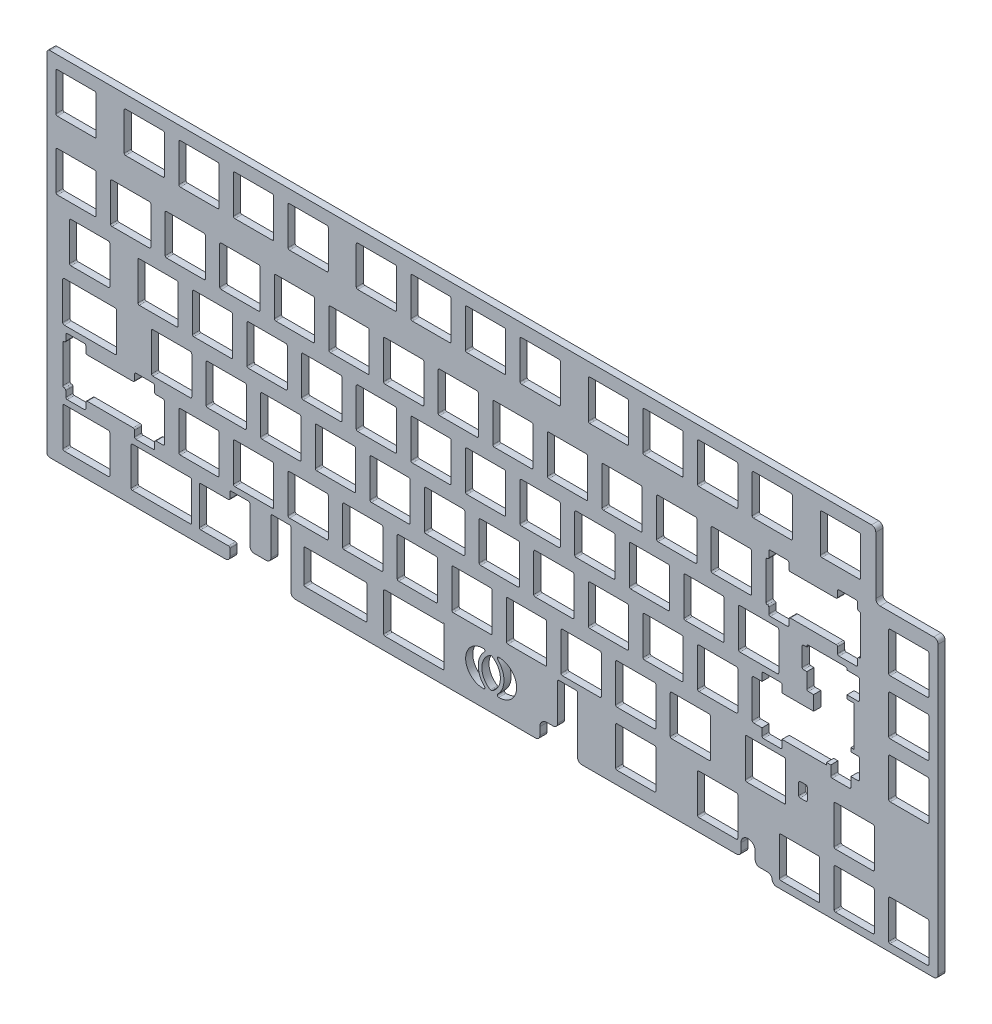
SolidWorks part; units mm, degrees
material "POM Acetal Copolymer"
ref_plane "Front Plane" through (0, 0, 0) normal (0, 0, 1) x (1, 0, 0)
ref_plane "Top Plane" through (0, 0, 0) normal (0, 1, 0) x (1, 0, 0)
ref_plane "Right Plane" through (0, 0, 0) normal (1, 0, 0) x (0, 0, -1)
sketch "Model" plane through (0, 0, 0) normal (0, 0, 1) x (1, 0, 0)
  line L0 (274.4928, 83.607) -> (287.4928, 83.607)
  line L1 (273.9928, 70.107) -> (273.9928, 75.3421)
  line L2 (8.8553, 129.8695) -> (8.8553, 63.082)
  line L3 (67.4518, 130.9695) -> (9.9553, 130.9695)
  line L4 (319.7678, 63.082) -> (319.7678, 106.4532)
  line L5 (195.4959, 7.957) -> (249.4928, 7.957)
  line L6 (86.9959, 28.958) -> (86.9959, 16.157)
  line L7 (187.4959, 29.458) -> (193.4959, 29.458)
  line L8 (193.9959, 28.958) -> (193.9959, 9.457)
  line L9 (186.9959, 16.157) -> (186.9959, 28.958)
  line L10 (87.4959, 29.458) -> (93.4959, 29.458)
  line L11 (126.357, 12.957) -> (126.357, 25.957)
  line L12 (62.0594, 12.957) -> (62.0594, 25.957)
  line L13 (38.2454, 12.957) -> (38.2454, 25.957)
  line L14 (14.4343, 12.957) -> (14.4343, 25.957)
  line L15 (72.207, 12.457) -> (62.5594, 12.457)
  line L16 (62.5594, 26.457) -> (72.207, 26.457)
  line L17 (59.3945, 25.957) -> (59.3945, 12.957)
  line L18 (58.8945, 12.457) -> (38.7454, 12.457)
  line L19 (38.7454, 26.457) -> (58.8945, 26.457)
  line L20 (30.8195, 25.957) -> (30.8195, 12.957)
  line L21 (30.3195, 12.457) -> (14.9343, 12.457)
  line L22 (14.9343, 26.457) -> (30.3195, 26.457)
  line L23 (93.9959, 28.958) -> (93.9959, 9.457)
  line L24 (146.9959, 12.457) -> (126.857, 12.457)
  line L25 (126.857, 26.457) -> (146.9959, 26.457)
  line L26 (147.4959, 26.7823) -> (147.4959, 12.957)
  line L27 (9.9553, 7.957) -> (71.207, 7.957)
  line L28 (95.4959, 7.957) -> (179.3625, 7.957)
  line L29 (263.3678, 5.0945) -> (318.2678, 5.0945)
  line L30 (180.8625, 12.157) -> (180.8625, 9.457)
  line L31 (250.9928, 12.157) -> (250.9928, 9.457)
  line L32 (255.9928, 12.157) -> (255.9928, 9.457)
  line L33 (183.3625, 14.657) -> (185.4959, 14.657)
  line L34 (81.207, 14.657) -> (85.4959, 14.657)
  line L35 (257.4928, 7.957) -> (260.371, 7.957)
  line L36 (8.8553, 63.082) -> (8.8553, 9.057)
  line L37 (319.7678, 63.082) -> (319.7678, 6.5945)
  line L38 (75.4518, 130.9695) -> (248.4268, 130.9695)
  line L39 (256.4268, 130.9695) -> (296.5553, 130.9695)
  line L40 (298.0553, 129.4695) -> (298.0553, 109.4532)
  line L41 (299.5553, 107.9532) -> (318.2678, 107.9532)
  line L42 (271.6572, 41.007) -> (273.6572, 41.007)
  line L43 (274.1572, 40.507) -> (274.1572, 36.507)
  line L44 (273.6572, 36.007) -> (271.6572, 36.007)
  line L45 (271.1572, 36.507) -> (271.1572, 40.507)
  line L46 (260.7295, 105.157) -> (260.7295, 103.157)
  line L47 (268.2295, 102.657) -> (284.2295, 102.657)
  line L48 (268.2295, 88.657) -> (284.2295, 88.657)
  line L49 (261.2295, 105.657) -> (267.2295, 105.657)
  line L50 (261.2295, 85.657) -> (267.2295, 85.657)
  line L51 (267.7295, 103.157) -> (267.7295, 105.157)
  line L52 (267.7295, 88.157) -> (267.7295, 86.157)
  line L53 (291.7295, 105.157) -> (291.7295, 103.157)
  line L54 (291.2295, 105.657) -> (285.2295, 105.657)
  line L55 (291.2295, 85.657) -> (285.2295, 85.657)
  line L56 (284.7295, 103.157) -> (284.7295, 105.157)
  line L57 (284.7295, 88.157) -> (284.7295, 86.157)
  line L58 (258.3508, 50.557) -> (258.3508, 48.057)
  line L59 (265.3508, 50.557) -> (280.8516, 50.557)
  line L60 (258.8508, 67.557) -> (264.8508, 67.557)
  line L61 (258.8508, 47.557) -> (264.8508, 47.557)
  line L62 (265.3508, 64.557) -> (265.3508, 67.057)
  line L63 (265.3508, 50.557) -> (265.3508, 48.057)
  line L64 (288.8508, 47.557) -> (282.8508, 47.557)
  line L65 (282.3508, 51.3421) -> (282.3508, 48.057)
  line L66 (15.4632, 48.0073) -> (15.4632, 46.007)
  line L67 (22.9632, 45.5073) -> (38.9632, 45.5073)
  line L68 (22.9632, 31.5073) -> (38.9632, 31.5073)
  line L69 (15.9632, 48.5073) -> (21.9632, 48.5073)
  line L70 (15.9632, 28.5073) -> (21.9632, 28.5073)
  line L71 (22.4632, 46.0073) -> (22.4632, 48.0073)
  line L72 (22.4632, 31.0073) -> (22.4632, 29.0073)
  line L73 (46.4632, 48.0073) -> (46.4632, 46.007)
  line L74 (45.9632, 48.5073) -> (39.9632, 48.5073)
  line L75 (45.9632, 28.5073) -> (39.9632, 28.5073)
  line L76 (39.4632, 46.0073) -> (39.4632, 48.0073)
  line L77 (39.4632, 31.0073) -> (39.4632, 29.0073)
  line L78 (258.3508, 50.557) -> (255.4453, 50.557)
  line L79 (276.3765, 69.607) -> (274.4928, 69.607)
  line L80 (276.3765, 64.557) -> (276.3765, 69.607)
  line L81 (292.3508, 82.2801) -> (292.3508, 75.8421)
  line L82 (292.3508, 58.2801) -> (292.3508, 51.8421)
  line L83 (291.8508, 82.7801) -> (287.9953, 82.7801)
  line L84 (255.4453, 64.557) -> (258.3508, 64.557)
  line L85 (290.3765, 74.0611) -> (290.3765, 60.0611)
  line L86 (254.9453, 64.057) -> (254.9453, 51.057)
  line L87 (287.9953, 75.3421) -> (291.8508, 75.3421)
  line L88 (289.3508, 58.7801) -> (291.8508, 58.7801)
  line L89 (290.3765, 74.0611) -> (287.9953, 74.0611)
  line L90 (287.9953, 74.0611) -> (287.9953, 75.3421)
  line L91 (289.3508, 58.7801) -> (289.3508, 60.0611)
  line L92 (289.3508, 60.0611) -> (290.3765, 60.0611)
  line L93 (282.3508, 51.3421) -> (280.8516, 51.3421)
  line L94 (280.8516, 51.3421) -> (280.8516, 50.557)
  line L95 (258.3508, 67.057) -> (258.3508, 64.557)
  line L96 (289.3508, 48.057) -> (289.3508, 51.3421)
  line L97 (291.8508, 51.3421) -> (289.3508, 51.3421)
  line L98 (287.9928, 83.107) -> (287.9953, 82.7801)
  line L99 (265.3508, 64.557) -> (276.3765, 64.557)
  line L100 (272.3508, 82.2801) -> (272.3508, 75.8421)
  line L101 (272.8508, 82.7801) -> (273.9928, 82.7801)
  line L102 (273.9928, 75.3421) -> (272.8508, 75.3421)
  line L103 (273.9928, 82.7801) -> (273.9928, 83.107)
  line L104 (259.7053, 89.157) -> (259.7053, 102.157)
  line L105 (292.7553, 102.157) -> (292.7553, 89.157)
  line L106 (291.7295, 86.157) -> (291.7295, 88.157)
  line L107 (292.2295, 88.657) -> (292.2553, 88.657)
  line L108 (292.2295, 102.657) -> (292.2553, 102.657)
  line L109 (260.2053, 102.657) -> (260.2295, 102.657)
  line L110 (260.7295, 86.157) -> (260.7295, 88.157)
  line L111 (260.2295, 88.657) -> (260.2053, 88.657)
  line L112 (49.8678, 45.007) -> (49.8678, 32.007)
  line L113 (46.4632, 29.0073) -> (46.4632, 31.007)
  line L114 (46.9632, 31.507) -> (49.3678, 31.507)
  line L115 (46.9632, 45.507) -> (49.3678, 45.507)
  line L116 (14.4365, 32.007) -> (14.4365, 45.007)
  line L117 (15.4632, 29.0073) -> (15.4632, 31.007)
  line L118 (14.9632, 31.507) -> (14.9365, 31.507)
  line L119 (14.9365, 45.507) -> (14.9632, 45.507)
  line L120 (79.707, 28.958) -> (79.707, 16.157)
  line L121 (72.707, 11.957) -> (72.707, 9.457)
  line L122 (72.707, 26.957) -> (72.707, 28.958)
  line L123 (73.207, 29.458) -> (79.207, 29.458)
  line L124 (120.5413, 13.957) -> (120.5413, 24.957)
  line L125 (99.0413, 13.457) -> (120.0413, 13.457)
  line L126 (98.5413, 24.957) -> (98.5413, 13.957)
  line L127 (120.0413, 25.457) -> (99.0413, 25.457)
  line L144 (12.5303, 112.4445) -> (25.5803, 112.4445)
  line L145 (26.0803, 112.9445) -> (26.0803, 125.9945)
  line L146 (25.5803, 126.4945) -> (12.5303, 126.4945)
  line L147 (12.0303, 125.9945) -> (12.0303, 112.9445)
  line L148 (36.3428, 112.4445) -> (49.3928, 112.4445)
  line L149 (49.8928, 112.9445) -> (49.8928, 125.9945)
  line L150 (49.3928, 126.4945) -> (36.3428, 126.4945)
  line L151 (35.8428, 125.9945) -> (35.8428, 112.9445)
  line L152 (93.4928, 112.4445) -> (106.5428, 112.4445)
  line L153 (107.0428, 112.9445) -> (107.0428, 125.9945)
  line L154 (106.5428, 126.4945) -> (93.4928, 126.4945)
  line L155 (92.9928, 125.9945) -> (92.9928, 112.9445)
  line L156 (117.3053, 112.4445) -> (130.3553, 112.4445)
  line L157 (130.8553, 112.9445) -> (130.8553, 125.9945)
  line L158 (130.3553, 126.4945) -> (117.3053, 126.4945)
  line L159 (116.8053, 125.9945) -> (116.8053, 112.9445)
  line L160 (136.3553, 112.4445) -> (149.4053, 112.4445)
  line L161 (149.9053, 112.9445) -> (149.9053, 125.9945)
  line L162 (149.4053, 126.4945) -> (136.3553, 126.4945)
  line L163 (135.8553, 125.9945) -> (135.8553, 112.9445)
  line L164 (155.4053, 112.4445) -> (168.4553, 112.4445)
  line L165 (168.9553, 112.9445) -> (168.9553, 125.9945)
  line L166 (168.4553, 126.4945) -> (155.4053, 126.4945)
  line L167 (154.9053, 125.9945) -> (154.9053, 112.9445)
  line L168 (174.4553, 112.4445) -> (187.5053, 112.4445)
  line L169 (188.0053, 112.9445) -> (188.0053, 125.9945)
  line L170 (187.5053, 126.4945) -> (174.4553, 126.4945)
  line L171 (173.9553, 125.9945) -> (173.9553, 112.9445)
  line L172 (198.2678, 112.4445) -> (211.3178, 112.4445)
  line L173 (211.8178, 112.9445) -> (211.8178, 125.9945)
  line L174 (211.3178, 126.4945) -> (198.2678, 126.4945)
  line L175 (197.7678, 125.9945) -> (197.7678, 112.9445)
  line L176 (217.3178, 112.4445) -> (230.3678, 112.4445)
  line L177 (230.8678, 112.9445) -> (230.8678, 125.9945)
  line L178 (230.3678, 126.4945) -> (217.3178, 126.4945)
  line L179 (216.8178, 125.9945) -> (216.8178, 112.9445)
  line L180 (279.2303, 112.4445) -> (292.2803, 112.4445)
  line L181 (292.7803, 112.9445) -> (292.7803, 125.9945)
  line L182 (292.2803, 126.4945) -> (279.2303, 126.4945)
  line L183 (278.7303, 125.9945) -> (278.7303, 112.9445)
  line L184 (303.0428, 88.632) -> (316.0928, 88.632)
  line L185 (316.5928, 89.132) -> (316.5928, 102.182)
  line L186 (316.0928, 102.682) -> (303.0428, 102.682)
  line L187 (302.5428, 102.182) -> (302.5428, 89.132)
  line L188 (283.9928, 26.7195) -> (297.0428, 26.7195)
  line L189 (297.5428, 27.2195) -> (297.5428, 40.2695)
  line L190 (297.0428, 40.7695) -> (283.9928, 40.7695)
  line L191 (283.4928, 40.2695) -> (283.4928, 27.2195)
  line L192 (303.0428, 7.6695) -> (316.0928, 7.6695)
  line L193 (316.5928, 8.1695) -> (316.5928, 21.2195)
  line L194 (316.0928, 21.7195) -> (303.0428, 21.7195)
  line L195 (302.5428, 21.2195) -> (302.5428, 8.1695)
  line L196 (283.9928, 7.6695) -> (297.0428, 7.6695)
  line L197 (297.5428, 8.1695) -> (297.5428, 21.2195)
  line L198 (297.0428, 21.7195) -> (283.9928, 21.7195)
  line L199 (283.4928, 21.2195) -> (283.4928, 8.1695)
  line L200 (264.9428, 7.6695) -> (277.9928, 7.6695)
  line L201 (278.4928, 8.1695) -> (278.4928, 21.2195)
  line L202 (277.9928, 21.7195) -> (264.9428, 21.7195)
  line L203 (264.4428, 21.2195) -> (264.4428, 8.1695)
  line L204 (236.3678, 12.432) -> (249.4178, 12.432)
  line L205 (249.9178, 12.932) -> (249.9178, 25.982)
  line L206 (249.4178, 26.482) -> (236.3678, 26.482)
  line L207 (235.8678, 25.982) -> (235.8678, 12.932)
  line L208 (207.7928, 12.432) -> (220.8428, 12.432)
  line L209 (221.3428, 12.932) -> (221.3428, 25.982)
  line L210 (220.8428, 26.482) -> (207.7928, 26.482)
  line L211 (207.2928, 25.982) -> (207.2928, 12.932)
  line L212 (253.0365, 31.482) -> (266.0865, 31.482)
  line L213 (266.5865, 31.982) -> (266.5865, 45.032)
  line L214 (266.0865, 45.532) -> (253.0365, 45.532)
  line L215 (252.5365, 45.032) -> (252.5365, 31.982)
  line L216 (226.8428, 31.482) -> (239.8928, 31.482)
  line L217 (240.3928, 31.982) -> (240.3928, 45.032)
  line L218 (239.8928, 45.532) -> (226.8428, 45.532)
  line L219 (226.3428, 45.032) -> (226.3428, 31.982)
  line L220 (207.7928, 31.482) -> (220.8428, 31.482)
  line L221 (221.3428, 31.982) -> (221.3428, 45.032)
  line L222 (220.8428, 45.532) -> (207.7928, 45.532)
  line L223 (207.2928, 45.032) -> (207.2928, 31.982)
  line L224 (188.7428, 31.482) -> (201.7928, 31.482)
  line L225 (202.2928, 31.982) -> (202.2928, 45.032)
  line L226 (201.7928, 45.532) -> (188.7428, 45.532)
  line L227 (188.2428, 45.032) -> (188.2428, 31.982)
  line L228 (169.6928, 31.482) -> (182.7428, 31.482)
  line L229 (183.2428, 31.982) -> (183.2428, 45.032)
  line L230 (182.7428, 45.532) -> (169.6928, 45.532)
  line L231 (169.1928, 45.032) -> (169.1928, 31.982)
  line L232 (150.6428, 31.482) -> (163.6928, 31.482)
  line L233 (164.1928, 31.982) -> (164.1928, 45.032)
  line L234 (163.6928, 45.532) -> (150.6428, 45.532)
  line L235 (150.1428, 45.032) -> (150.1428, 31.982)
  line L236 (131.5928, 31.482) -> (144.6428, 31.482)
  line L237 (145.1428, 31.982) -> (145.1428, 45.032)
  line L238 (144.6428, 45.532) -> (131.5928, 45.532)
  line L239 (131.0928, 45.032) -> (131.0928, 31.982)
  line L240 (112.5428, 31.482) -> (125.5928, 31.482)
  line L241 (126.0928, 31.982) -> (126.0928, 45.032)
  line L242 (125.5928, 45.532) -> (112.5428, 45.532)
  line L243 (112.0428, 45.032) -> (112.0428, 31.982)
  line L244 (93.4928, 31.482) -> (106.5428, 31.482)
  line L245 (107.0428, 31.982) -> (107.0428, 45.032)
  line L246 (106.5428, 45.532) -> (93.4928, 45.532)
  line L247 (92.9928, 45.032) -> (92.9928, 31.982)
  line L248 (74.4428, 31.482) -> (87.4928, 31.482)
  line L249 (87.9928, 31.982) -> (87.9928, 45.032)
  line L250 (87.4928, 45.532) -> (74.4428, 45.532)
  line L251 (73.9428, 45.032) -> (73.9428, 31.982)
  line L252 (55.3928, 31.482) -> (68.4428, 31.482)
  line L253 (68.9428, 31.982) -> (68.9428, 45.032)
  line L254 (68.4428, 45.532) -> (55.3928, 45.532)
  line L255 (54.8928, 45.032) -> (54.8928, 31.982)
  line L256 (45.8678, 50.532) -> (58.9178, 50.532)
  line L257 (59.4178, 51.032) -> (59.4178, 64.082)
  line L258 (58.9178, 64.582) -> (45.8678, 64.582)
  line L259 (45.3678, 64.082) -> (45.3678, 51.032)
  line L260 (64.9178, 50.532) -> (77.9678, 50.532)
  line L261 (78.4678, 51.032) -> (78.4678, 64.082)
  line L262 (77.9678, 64.582) -> (64.9178, 64.582)
  line L263 (64.4178, 64.082) -> (64.4178, 51.032)
  line L264 (83.9678, 50.532) -> (97.0178, 50.532)
  line L265 (97.5178, 51.032) -> (97.5178, 64.082)
  line L266 (97.0178, 64.582) -> (83.9678, 64.582)
  line L267 (83.4678, 64.082) -> (83.4678, 51.032)
  line L268 (103.0178, 50.532) -> (116.0678, 50.532)
  line L269 (116.5678, 51.032) -> (116.5678, 64.082)
  line L270 (116.0678, 64.582) -> (103.0178, 64.582)
  line L271 (102.5178, 64.082) -> (102.5178, 51.032)
  line L272 (122.0678, 50.532) -> (135.1178, 50.532)
  line L273 (135.6178, 51.032) -> (135.6178, 64.082)
  line L274 (135.1178, 64.582) -> (122.0678, 64.582)
  line L275 (121.5678, 64.082) -> (121.5678, 51.032)
  line L276 (141.1178, 50.532) -> (154.1678, 50.532)
  line L277 (154.6678, 51.032) -> (154.6678, 64.082)
  line L278 (154.1678, 64.582) -> (141.1178, 64.582)
  line L279 (140.6178, 64.082) -> (140.6178, 51.032)
  line L280 (160.1678, 50.532) -> (173.2178, 50.532)
  line L281 (173.7178, 51.032) -> (173.7178, 64.082)
  line L282 (173.2178, 64.582) -> (160.1678, 64.582)
  line L283 (159.6678, 64.082) -> (159.6678, 51.032)
  line L284 (179.2178, 50.532) -> (192.2678, 50.532)
  line L285 (192.7678, 51.032) -> (192.7678, 64.082)
  line L286 (192.2678, 64.582) -> (179.2178, 64.582)
  line L287 (178.7178, 64.082) -> (178.7178, 51.032)
  line L288 (198.2678, 50.532) -> (211.3178, 50.532)
  line L289 (211.8178, 51.032) -> (211.8178, 64.082)
  line L290 (211.3178, 64.582) -> (198.2678, 64.582)
  line L291 (197.7678, 64.082) -> (197.7678, 51.032)
  line L292 (217.3178, 50.532) -> (230.3678, 50.532)
  line L293 (230.8678, 51.032) -> (230.8678, 64.082)
  line L294 (230.3678, 64.582) -> (217.3178, 64.582)
  line L295 (216.8178, 64.082) -> (216.8178, 51.032)
  line L296 (236.3678, 50.532) -> (249.4178, 50.532)
  line L297 (249.9178, 51.032) -> (249.9178, 64.082)
  line L298 (249.4178, 64.582) -> (236.3678, 64.582)
  line L299 (235.8678, 64.082) -> (235.8678, 51.032)
  line L300 (17.2928, 69.582) -> (30.3428, 69.582)
  line L301 (30.8428, 70.082) -> (30.8428, 83.132)
  line L302 (30.3428, 83.632) -> (17.2928, 83.632)
  line L303 (16.7928, 83.132) -> (16.7928, 70.082)
  line L304 (12.5303, 88.632) -> (25.5803, 88.632)
  line L305 (26.0803, 89.132) -> (26.0803, 102.182)
  line L306 (25.5803, 102.682) -> (12.5303, 102.682)
  line L307 (12.0303, 102.182) -> (12.0303, 89.132)
  line L308 (31.5803, 88.632) -> (44.6303, 88.632)
  line L309 (45.1303, 89.132) -> (45.1303, 102.182)
  line L310 (44.6303, 102.682) -> (31.5803, 102.682)
  line L311 (31.0803, 102.182) -> (31.0803, 89.132)
  line L312 (50.6303, 88.632) -> (63.6803, 88.632)
  line L313 (64.1803, 89.132) -> (64.1803, 102.182)
  line L314 (63.6803, 102.682) -> (50.6303, 102.682)
  line L315 (50.1303, 102.182) -> (50.1303, 89.132)
  line L316 (69.6803, 88.632) -> (82.7303, 88.632)
  line L317 (83.2303, 89.132) -> (83.2303, 102.182)
  line L318 (82.7303, 102.682) -> (69.6803, 102.682)
  line L319 (69.1803, 102.182) -> (69.1803, 89.132)
  line L320 (88.7303, 88.632) -> (101.7803, 88.632)
  line L321 (102.2803, 89.132) -> (102.2803, 102.182)
  line L322 (101.7803, 102.682) -> (88.7303, 102.682)
  line L323 (88.2303, 102.182) -> (88.2303, 89.132)
  line L324 (107.7803, 88.632) -> (120.8303, 88.632)
  line L325 (121.3303, 89.132) -> (121.3303, 102.182)
  line L326 (120.8303, 102.682) -> (107.7803, 102.682)
  line L327 (107.2803, 102.182) -> (107.2803, 89.132)
  line L328 (126.8303, 88.632) -> (139.8803, 88.632)
  line L329 (140.3803, 89.132) -> (140.3803, 102.182)
  line L330 (139.8803, 102.682) -> (126.8303, 102.682)
  line L331 (126.3303, 102.182) -> (126.3303, 89.132)
  line L332 (145.8803, 88.632) -> (158.9303, 88.632)
  line L333 (159.4303, 89.132) -> (159.4303, 102.182)
  line L334 (158.9303, 102.682) -> (145.8803, 102.682)
  line L335 (145.3803, 102.182) -> (145.3803, 89.132)
  line L336 (164.9303, 88.632) -> (177.9803, 88.632)
  line L337 (178.4803, 89.132) -> (178.4803, 102.182)
  line L338 (177.9803, 102.682) -> (164.9303, 102.682)
  line L339 (164.4303, 102.182) -> (164.4303, 89.132)
  line L340 (183.9803, 88.632) -> (197.0303, 88.632)
  line L341 (197.5303, 89.132) -> (197.5303, 102.182)
  line L342 (197.0303, 102.682) -> (183.9803, 102.682)
  line L343 (183.4803, 102.182) -> (183.4803, 89.132)
  line L344 (203.0303, 88.632) -> (216.0803, 88.632)
  line L345 (216.5803, 89.132) -> (216.5803, 102.182)
  line L346 (216.0803, 102.682) -> (203.0303, 102.682)
  line L347 (202.5303, 102.182) -> (202.5303, 89.132)
  line L348 (222.0803, 88.632) -> (235.1303, 88.632)
  line L349 (235.6303, 89.132) -> (235.6303, 102.182)
  line L350 (235.1303, 102.682) -> (222.0803, 102.682)
  line L351 (221.5803, 102.182) -> (221.5803, 89.132)
  line L352 (241.1303, 88.632) -> (254.1803, 88.632)
  line L353 (254.6803, 89.132) -> (254.6803, 102.182)
  line L354 (254.1803, 102.682) -> (241.1303, 102.682)
  line L355 (240.6303, 102.182) -> (240.6303, 89.132)
  line L356 (41.1053, 69.582) -> (54.1553, 69.582)
  line L357 (54.6553, 70.082) -> (54.6553, 83.132)
  line L358 (54.1553, 83.632) -> (41.1053, 83.632)
  line L359 (40.6053, 83.132) -> (40.6053, 70.082)
  line L360 (60.1553, 69.582) -> (73.2053, 69.582)
  line L361 (73.7053, 70.082) -> (73.7053, 83.132)
  line L362 (73.2053, 83.632) -> (60.1553, 83.632)
  line L363 (59.6553, 83.132) -> (59.6553, 70.082)
  line L364 (79.2053, 69.582) -> (92.2553, 69.582)
  line L365 (92.7553, 70.082) -> (92.7553, 83.132)
  line L366 (92.2553, 83.632) -> (79.2053, 83.632)
  line L367 (78.7053, 83.132) -> (78.7053, 70.082)
  line L368 (98.2553, 69.582) -> (111.3053, 69.582)
  line L369 (111.8053, 70.082) -> (111.8053, 83.132)
  line L370 (111.3053, 83.632) -> (98.2553, 83.632)
  line L371 (97.7553, 83.132) -> (97.7553, 70.082)
  line L372 (117.3053, 69.582) -> (130.3553, 69.582)
  line L373 (130.8553, 70.082) -> (130.8553, 83.132)
  line L374 (130.3553, 83.632) -> (117.3053, 83.632)
  line L375 (116.8053, 83.132) -> (116.8053, 70.082)
  line L376 (136.3553, 69.582) -> (149.4053, 69.582)
  line L377 (149.9053, 70.082) -> (149.9053, 83.132)
  line L378 (149.4053, 83.632) -> (136.3553, 83.632)
  line L379 (135.8553, 83.132) -> (135.8553, 70.082)
  line L380 (155.4053, 69.582) -> (168.4553, 69.582)
  line L381 (168.9553, 70.082) -> (168.9553, 83.132)
  line L382 (168.4553, 83.632) -> (155.4053, 83.632)
  line L383 (154.9053, 83.132) -> (154.9053, 70.082)
  line L384 (174.4553, 69.582) -> (187.5053, 69.582)
  line L385 (188.0053, 70.082) -> (188.0053, 83.132)
  line L386 (187.5053, 83.632) -> (174.4553, 83.632)
  line L387 (173.9553, 83.132) -> (173.9553, 70.082)
  line L388 (193.5053, 69.582) -> (206.5553, 69.582)
  line L389 (207.0553, 70.082) -> (207.0553, 83.132)
  line L390 (206.5553, 83.632) -> (193.5053, 83.632)
  line L391 (193.0053, 83.132) -> (193.0053, 70.082)
  line L392 (212.5553, 69.582) -> (225.6053, 69.582)
  line L393 (226.1053, 70.082) -> (226.1053, 83.132)
  line L394 (225.6053, 83.632) -> (212.5553, 83.632)
  line L395 (212.0553, 83.132) -> (212.0553, 70.082)
  line L396 (231.6053, 69.582) -> (244.6553, 69.582)
  line L397 (245.1553, 70.082) -> (245.1553, 83.132)
  line L398 (244.6553, 83.632) -> (231.6053, 83.632)
  line L399 (231.1053, 83.132) -> (231.1053, 70.082)
  line L400 (250.6553, 69.582) -> (263.7053, 69.582)
  line L401 (264.2053, 70.082) -> (264.2053, 83.132)
  line L402 (263.7053, 83.632) -> (250.6553, 83.632)
  line L403 (250.1553, 83.132) -> (250.1553, 70.082)
  line L404 (303.0428, 69.582) -> (316.0928, 69.582)
  line L405 (316.5928, 70.082) -> (316.5928, 83.132)
  line L406 (316.0928, 83.632) -> (303.0428, 83.632)
  line L407 (302.5428, 83.132) -> (302.5428, 70.082)
  line L408 (303.0678, 64.582) -> (316.1178, 64.582)
  line L409 (302.5428, 51.057) -> (302.5428, 64.057)
  line L410 (316.0678, 50.532) -> (303.0678, 50.532)
  line L411 (316.5928, 64.107) -> (316.5928, 51.057)
  line L412 (32.699, 50.507) -> (14.9365, 50.507)
  line L413 (33.249, 64.057) -> (33.249, 51.057)
  line L414 (14.9365, 64.607) -> (32.699, 64.607)
  line L415 (14.3865, 51.057) -> (14.3865, 64.057)
  line L416 (236.3678, 112.4445) -> (249.4178, 112.4445)
  line L417 (249.9178, 112.9445) -> (249.9178, 125.9945)
  line L418 (249.4178, 126.4945) -> (236.3678, 126.4945)
  line L419 (235.8678, 125.9945) -> (235.8678, 112.9445)
  line L420 (255.4178, 112.4445) -> (268.4678, 112.4445)
  line L421 (268.9678, 112.9445) -> (268.9678, 125.9945)
  line L422 (268.4678, 126.4945) -> (255.4178, 126.4945)
  line L423 (254.9178, 125.9945) -> (254.9178, 112.9445)
  line L424 (55.3928, 112.4445) -> (68.4428, 112.4445)
  line L425 (68.9428, 112.9445) -> (68.9428, 125.9945)
  line L426 (68.4428, 126.4945) -> (55.3928, 126.4945)
  line L427 (54.8928, 125.9945) -> (54.8928, 112.9445)
  line L428 (74.4428, 112.4445) -> (87.4928, 112.4445)
  line L429 (87.9928, 112.9445) -> (87.9928, 125.9945)
  line L430 (87.4928, 126.4945) -> (74.4428, 126.4945)
  line L431 (73.9428, 125.9945) -> (73.9428, 112.9445)
  line L432 (67.4518, 130.9695) -> (75.4518, 130.9695)
  line L433 (248.4268, 130.9695) -> (256.4268, 130.9695)
  arc A0 (319.7678, 106.4532) -> (318.2678, 107.9532) centre (318.2678, 106.4532) ccw
  arc A1 (318.2678, 5.0945) -> (319.7678, 6.5945) centre (318.2678, 6.5945) ccw
  arc A2 (193.9959, 9.457) -> (195.4959, 7.957) centre (195.4959, 9.457) ccw
  arc A3 (273.9928, 70.107) -> (274.4928, 69.607) centre (274.4928, 70.107) ccw
  arc A4 (287.9928, 83.107) -> (287.4928, 83.607) centre (287.4928, 83.107) ccw
  arc A5 (274.4928, 83.607) -> (273.9928, 83.107) centre (274.4928, 83.107) ccw
  arc A6 (8.8553, 9.057) -> (9.9553, 7.957) centre (9.9553, 9.057) ccw
  arc A7 (9.9553, 130.9695) -> (8.8553, 129.8695) centre (9.9553, 129.8695) ccw
  arc A8 (85.4959, 14.657) -> (86.9959, 16.157) centre (85.4959, 16.157) ccw
  arc A9 (193.9959, 28.958) -> (193.4959, 29.458) centre (193.4959, 28.958) ccw
  arc A10 (187.4959, 29.458) -> (186.9959, 28.958) centre (187.4959, 28.958) ccw
  arc A11 (185.4959, 14.657) -> (186.9959, 16.157) centre (185.4959, 16.157) ccw
  arc A12 (87.4959, 29.458) -> (86.9959, 28.958) centre (87.4959, 28.958) ccw
  arc A13 (126.357, 12.957) -> (126.857, 12.457) centre (126.857, 12.957) ccw
  arc A14 (93.9959, 28.958) -> (93.4959, 29.458) centre (93.4959, 28.958) ccw
  arc A15 (38.7454, 26.457) -> (38.2454, 25.957) centre (38.7454, 25.957) ccw
  arc A16 (14.9343, 26.457) -> (14.4343, 25.957) centre (14.9343, 25.957) ccw
  arc A17 (62.0594, 12.957) -> (62.5594, 12.457) centre (62.5594, 12.957) ccw
  arc A18 (62.5594, 26.457) -> (62.0594, 25.957) centre (62.5594, 25.957) ccw
  arc A19 (38.2454, 12.957) -> (38.7454, 12.457) centre (38.7454, 12.957) ccw
  arc A20 (58.8945, 12.457) -> (59.3945, 12.957) centre (58.8945, 12.957) ccw
  arc A21 (59.3945, 25.957) -> (58.8945, 26.457) centre (58.8945, 25.957) ccw
  arc A22 (30.3195, 12.457) -> (30.8195, 12.957) centre (30.3195, 12.957) ccw
  arc A23 (14.4343, 12.957) -> (14.9343, 12.457) centre (14.9343, 12.957) ccw
  arc A24 (30.8195, 25.957) -> (30.3195, 26.457) centre (30.3195, 25.957) ccw
  arc A25 (126.857, 26.457) -> (126.357, 25.957) centre (126.857, 25.957) ccw
  arc A26 (146.9959, 12.457) -> (147.4959, 12.957) centre (146.9959, 12.957) ccw
  arc A27 (147.4959, 26.7823) -> (146.9959, 26.457) centre (147.4647, 26.2833) ccw
  arc A28 (93.9959, 9.457) -> (95.4959, 7.957) centre (95.4959, 9.457) ccw
  arc A29 (261.8694, 6.5258) -> (263.3678, 5.0945) centre (263.3678, 6.5945) ccw
  arc A30 (261.8694, 6.5258) -> (260.371, 7.957) centre (260.371, 6.457) ccw
  arc A31 (179.3625, 7.957) -> (180.8625, 9.457) centre (179.3625, 9.457) ccw
  arc A32 (255.9928, 9.457) -> (257.4928, 7.957) centre (257.4928, 9.457) ccw
  arc A33 (249.4928, 7.957) -> (250.9928, 9.457) centre (249.4928, 9.457) ccw
  arc A34 (255.9928, 12.157) -> (250.9928, 12.157) centre (253.4928, 12.157) ccw
  arc A35 (183.3625, 14.657) -> (180.8625, 12.157) centre (183.3625, 12.157) ccw
  arc A36 (298.0553, 129.4695) -> (296.5553, 130.9695) centre (296.5553, 129.4695) ccw
  arc A37 (298.0553, 109.4532) -> (299.5553, 107.9532) centre (299.5553, 109.4532) ccw
  arc A38 (271.6572, 41.007) -> (271.1572, 40.507) centre (271.6572, 40.507) ccw
  arc A39 (274.1572, 40.507) -> (273.6572, 41.007) centre (273.6572, 40.507) ccw
  arc A40 (273.6572, 36.007) -> (274.1572, 36.507) centre (273.6572, 36.507) ccw
  arc A41 (271.1572, 36.507) -> (271.6572, 36.007) centre (271.6572, 36.507) ccw
  arc A42 (260.2295, 102.657) -> (260.7295, 103.157) centre (260.2295, 103.157) ccw
  arc A43 (267.7295, 103.157) -> (268.2295, 102.657) centre (268.2295, 103.157) ccw
  arc A44 (261.2295, 105.657) -> (260.7295, 105.157) centre (261.2295, 105.157) ccw
  arc A45 (260.7295, 86.157) -> (261.2295, 85.657) centre (261.2295, 86.157) ccw
  arc A46 (267.7295, 105.157) -> (267.2295, 105.657) centre (267.2295, 105.157) ccw
  arc A47 (268.2295, 88.657) -> (267.7295, 88.157) centre (268.2295, 88.157) ccw
  arc A48 (267.2295, 85.657) -> (267.7295, 86.157) centre (267.2295, 86.157) ccw
  arc A49 (284.2295, 102.657) -> (284.7295, 103.157) centre (284.2295, 103.157) ccw
  arc A50 (291.7295, 105.157) -> (291.2295, 105.657) centre (291.2295, 105.157) ccw
  arc A51 (291.2295, 85.657) -> (291.7295, 86.157) centre (291.2295, 86.157) ccw
  arc A52 (285.2295, 105.657) -> (284.7295, 105.157) centre (285.2295, 105.157) ccw
  arc A53 (284.7295, 88.157) -> (284.2295, 88.657) centre (284.2295, 88.157) ccw
  arc A54 (284.7295, 86.157) -> (285.2295, 85.657) centre (285.2295, 86.157) ccw
  arc A55 (258.8508, 67.557) -> (258.3508, 67.057) centre (258.8508, 67.057) ccw
  arc A56 (258.3508, 48.057) -> (258.8508, 47.557) centre (258.8508, 48.057) ccw
  arc A57 (265.3508, 67.057) -> (264.8508, 67.557) centre (264.8508, 67.057) ccw
  arc A58 (264.8508, 47.557) -> (265.3508, 48.057) centre (264.8508, 48.057) ccw
  arc A59 (288.8508, 47.557) -> (289.3508, 48.057) centre (288.8508, 48.057) ccw
  arc A60 (282.3508, 48.057) -> (282.8508, 47.557) centre (282.8508, 48.057) ccw
  arc A61 (14.9632, 45.507) -> (15.4632, 46.007) centre (14.9632, 46.007) ccw
  arc A62 (22.4632, 46.0073) -> (22.9632, 45.5073) centre (22.9632, 46.0073) ccw
  arc A63 (15.9632, 48.5073) -> (15.4632, 48.0073) centre (15.9632, 48.0073) ccw
  arc A64 (15.4632, 29.0073) -> (15.9632, 28.5073) centre (15.9632, 29.0073) ccw
  arc A65 (22.4632, 48.0073) -> (21.9632, 48.5073) centre (21.9632, 48.0073) ccw
  arc A66 (22.9632, 31.5073) -> (22.4632, 31.0073) centre (22.9632, 31.0073) ccw
  arc A67 (21.9632, 28.5073) -> (22.4632, 29.0073) centre (21.9632, 29.0073) ccw
  arc A68 (38.9632, 45.5073) -> (39.4632, 46.0073) centre (38.9632, 46.0073) ccw
  arc A69 (46.4632, 48.0073) -> (45.9632, 48.5073) centre (45.9632, 48.0073) ccw
  arc A70 (45.9632, 28.5073) -> (46.4632, 29.0073) centre (45.9632, 29.0073) ccw
  arc A71 (39.9632, 48.5073) -> (39.4632, 48.0073) centre (39.9632, 48.0073) ccw
  arc A72 (39.4632, 31.0073) -> (38.9632, 31.5073) centre (38.9632, 31.0073) ccw
  arc A73 (39.4632, 29.0073) -> (39.9632, 28.5073) centre (39.9632, 29.0073) ccw
  arc A74 (291.8508, 51.3421) -> (292.3508, 51.8421) centre (291.8508, 51.8421) ccw
  arc A75 (292.3508, 82.2801) -> (291.8508, 82.7801) centre (291.8508, 82.2801) ccw
  arc A76 (292.3508, 58.2801) -> (291.8508, 58.7801) centre (291.8508, 58.2801) ccw
  arc A77 (291.8508, 75.3421) -> (292.3508, 75.8421) centre (291.8508, 75.8421) ccw
  arc A78 (272.8508, 82.7801) -> (272.3508, 82.2801) centre (272.8508, 82.2801) ccw
  arc A79 (272.3508, 75.8421) -> (272.8508, 75.3421) centre (272.8508, 75.8421) ccw
  arc A80 (259.7053, 89.157) -> (260.2053, 88.657) centre (260.2053, 89.157) ccw
  arc A81 (260.2053, 102.657) -> (259.7053, 102.157) centre (260.2053, 102.157) ccw
  arc A82 (292.2553, 88.657) -> (292.7553, 89.157) centre (292.2553, 89.157) ccw
  arc A83 (292.7553, 102.157) -> (292.2553, 102.657) centre (292.2553, 102.157) ccw
  arc A84 (292.2295, 88.657) -> (291.7295, 88.157) centre (292.2295, 88.157) ccw
  arc A85 (291.7295, 103.157) -> (292.2295, 102.657) centre (292.2295, 103.157) ccw
  arc A86 (260.7295, 88.157) -> (260.2295, 88.657) centre (260.2295, 88.157) ccw
  arc A87 (49.3678, 31.507) -> (49.8678, 32.007) centre (49.3678, 32.007) ccw
  arc A88 (49.8678, 45.007) -> (49.3678, 45.507) centre (49.3678, 45.007) ccw
  arc A89 (46.9632, 31.507) -> (46.4632, 31.007) centre (46.9632, 31.007) ccw
  arc A90 (46.4632, 46.007) -> (46.9632, 45.507) centre (46.9632, 46.007) ccw
  arc A91 (14.4365, 32.007) -> (14.9365, 31.507) centre (14.9365, 32.007) ccw
  arc A92 (14.9365, 45.507) -> (14.4365, 45.007) centre (14.9365, 45.007) ccw
  arc A93 (15.4632, 31.007) -> (14.9632, 31.507) centre (14.9632, 31.007) ccw
  arc A94 (72.707, 11.957) -> (72.207, 12.457) centre (72.207, 11.957) ccw
  arc A95 (72.207, 26.457) -> (72.707, 26.957) centre (72.207, 26.957) ccw
  arc A96 (73.207, 29.458) -> (72.707, 28.958) centre (73.207, 28.958) ccw
  arc A97 (79.707, 28.958) -> (79.207, 29.458) centre (79.207, 28.958) ccw
  arc A98 (71.207, 7.957) -> (72.707, 9.457) centre (71.207, 9.457) ccw
  arc A99 (79.707, 16.157) -> (81.207, 14.657) centre (81.207, 16.157) ccw
  arc A100 (255.4453, 64.557) -> (254.9453, 64.057) centre (255.4453, 64.057) ccw
  arc A101 (254.9453, 51.057) -> (255.4453, 50.557) centre (255.4453, 51.057) ccw
  arc A102 (120.0413, 13.457) -> (120.5413, 13.957) centre (120.0413, 13.957) ccw
  arc A103 (98.5413, 13.957) -> (99.0413, 13.457) centre (99.0413, 13.957) ccw
  arc A104 (99.0413, 25.457) -> (98.5413, 24.957) centre (99.0413, 24.957) ccw
  arc A105 (120.5413, 24.957) -> (120.0413, 25.457) centre (120.0413, 24.957) ccw
  circle A106 centre (161.0365, 19.8697) radius 6.0649
  circle A107 centre (166.6822, 19.8697) radius 6.0649
  circle A108 centre (161.0365, 19.8697) radius 7.3149
  circle A109 centre (166.6822, 19.8697) radius 7.3149
  arc A134 (303.0678, 64.582) -> (302.5428, 64.057) centre (303.0678, 64.057) ccw
  arc A135 (302.5428, 51.057) -> (303.0678, 50.532) centre (303.0678, 51.057) ccw
  arc A136 (316.0678, 50.532) -> (316.5928, 51.057) centre (316.0678, 51.057) ccw
  arc A137 (316.5928, 64.107) -> (316.1178, 64.582) centre (316.1178, 64.107) ccw
  arc A138 (14.3865, 51.057) -> (14.9365, 50.507) centre (14.9365, 51.057) ccw
  arc A139 (32.699, 50.507) -> (33.249, 51.057) centre (32.699, 51.057) ccw
  arc A140 (33.249, 64.057) -> (32.699, 64.607) centre (32.699, 64.057) ccw
  arc A141 (14.9365, 64.607) -> (14.3865, 64.057) centre (14.9365, 64.057) ccw
  arc A142 (25.5803, 112.4445) -> (26.0803, 112.9445) centre (25.5803, 112.9445) ccw
  arc A143 (26.0803, 125.9945) -> (25.5803, 126.4945) centre (25.5803, 125.9945) ccw
  arc A144 (12.5303, 126.4945) -> (12.0303, 125.9945) centre (12.5303, 125.9945) ccw
  arc A145 (12.0303, 112.9445) -> (12.5303, 112.4445) centre (12.5303, 112.9445) ccw
  arc A146 (49.3928, 112.4445) -> (49.8928, 112.9445) centre (49.3928, 112.9445) ccw
  arc A147 (49.8928, 125.9945) -> (49.3928, 126.4945) centre (49.3928, 125.9945) ccw
  arc A148 (36.3428, 126.4945) -> (35.8428, 125.9945) centre (36.3428, 125.9945) ccw
  arc A149 (35.8428, 112.9445) -> (36.3428, 112.4445) centre (36.3428, 112.9445) ccw
  arc A150 (106.5428, 112.4445) -> (107.0428, 112.9445) centre (106.5428, 112.9445) ccw
  arc A151 (107.0428, 125.9945) -> (106.5428, 126.4945) centre (106.5428, 125.9945) ccw
  arc A152 (93.4928, 126.4945) -> (92.9928, 125.9945) centre (93.4928, 125.9945) ccw
  arc A153 (92.9928, 112.9445) -> (93.4928, 112.4445) centre (93.4928, 112.9445) ccw
  arc A154 (130.3553, 112.4445) -> (130.8553, 112.9445) centre (130.3553, 112.9445) ccw
  arc A155 (130.8553, 125.9945) -> (130.3553, 126.4945) centre (130.3553, 125.9945) ccw
  arc A156 (117.3053, 126.4945) -> (116.8053, 125.9945) centre (117.3053, 125.9945) ccw
  arc A157 (116.8053, 112.9445) -> (117.3053, 112.4445) centre (117.3053, 112.9445) ccw
  arc A158 (149.4053, 112.4445) -> (149.9053, 112.9445) centre (149.4053, 112.9445) ccw
  arc A159 (149.9053, 125.9945) -> (149.4053, 126.4945) centre (149.4053, 125.9945) ccw
  arc A160 (136.3553, 126.4945) -> (135.8553, 125.9945) centre (136.3553, 125.9945) ccw
  arc A161 (135.8553, 112.9445) -> (136.3553, 112.4445) centre (136.3553, 112.9445) ccw
  arc A162 (168.4553, 112.4445) -> (168.9553, 112.9445) centre (168.4553, 112.9445) ccw
  arc A163 (168.9553, 125.9945) -> (168.4553, 126.4945) centre (168.4553, 125.9945) ccw
  arc A164 (155.4053, 126.4945) -> (154.9053, 125.9945) centre (155.4053, 125.9945) ccw
  arc A165 (154.9053, 112.9445) -> (155.4053, 112.4445) centre (155.4053, 112.9445) ccw
  arc A166 (187.5053, 112.4445) -> (188.0053, 112.9445) centre (187.5053, 112.9445) ccw
  arc A167 (188.0053, 125.9945) -> (187.5053, 126.4945) centre (187.5053, 125.9945) ccw
  arc A168 (174.4553, 126.4945) -> (173.9553, 125.9945) centre (174.4553, 125.9945) ccw
  arc A169 (173.9553, 112.9445) -> (174.4553, 112.4445) centre (174.4553, 112.9445) ccw
  arc A170 (211.3178, 112.4445) -> (211.8178, 112.9445) centre (211.3178, 112.9445) ccw
  arc A171 (211.8178, 125.9945) -> (211.3178, 126.4945) centre (211.3178, 125.9945) ccw
  arc A172 (198.2678, 126.4945) -> (197.7678, 125.9945) centre (198.2678, 125.9945) ccw
  arc A173 (197.7678, 112.9445) -> (198.2678, 112.4445) centre (198.2678, 112.9445) ccw
  arc A174 (230.3678, 112.4445) -> (230.8678, 112.9445) centre (230.3678, 112.9445) ccw
  arc A175 (230.8678, 125.9945) -> (230.3678, 126.4945) centre (230.3678, 125.9945) ccw
  arc A176 (217.3178, 126.4945) -> (216.8178, 125.9945) centre (217.3178, 125.9945) ccw
  arc A177 (216.8178, 112.9445) -> (217.3178, 112.4445) centre (217.3178, 112.9445) ccw
  arc A178 (292.2803, 112.4445) -> (292.7803, 112.9445) centre (292.2803, 112.9445) ccw
  arc A179 (292.7803, 125.9945) -> (292.2803, 126.4945) centre (292.2803, 125.9945) ccw
  arc A180 (279.2303, 126.4945) -> (278.7303, 125.9945) centre (279.2303, 125.9945) ccw
  arc A181 (278.7303, 112.9445) -> (279.2303, 112.4445) centre (279.2303, 112.9445) ccw
  arc A182 (316.0928, 88.632) -> (316.5928, 89.132) centre (316.0928, 89.132) ccw
  arc A183 (316.5928, 102.182) -> (316.0928, 102.682) centre (316.0928, 102.182) ccw
  arc A184 (303.0428, 102.682) -> (302.5428, 102.182) centre (303.0428, 102.182) ccw
  arc A185 (302.5428, 89.132) -> (303.0428, 88.632) centre (303.0428, 89.132) ccw
  arc A186 (297.0428, 26.7195) -> (297.5428, 27.2195) centre (297.0428, 27.2195) ccw
  arc A187 (297.5428, 40.2695) -> (297.0428, 40.7695) centre (297.0428, 40.2695) ccw
  arc A188 (283.9928, 40.7695) -> (283.4928, 40.2695) centre (283.9928, 40.2695) ccw
  arc A189 (283.4928, 27.2195) -> (283.9928, 26.7195) centre (283.9928, 27.2195) ccw
  arc A190 (316.0928, 7.6695) -> (316.5928, 8.1695) centre (316.0928, 8.1695) ccw
  arc A191 (316.5928, 21.2195) -> (316.0928, 21.7195) centre (316.0928, 21.2195) ccw
  arc A192 (303.0428, 21.7195) -> (302.5428, 21.2195) centre (303.0428, 21.2195) ccw
  arc A193 (302.5428, 8.1695) -> (303.0428, 7.6695) centre (303.0428, 8.1695) ccw
  arc A194 (297.0428, 7.6695) -> (297.5428, 8.1695) centre (297.0428, 8.1695) ccw
  arc A195 (297.5428, 21.2195) -> (297.0428, 21.7195) centre (297.0428, 21.2195) ccw
  arc A196 (283.9928, 21.7195) -> (283.4928, 21.2195) centre (283.9928, 21.2195) ccw
  arc A197 (283.4928, 8.1695) -> (283.9928, 7.6695) centre (283.9928, 8.1695) ccw
  arc A198 (277.9928, 7.6695) -> (278.4928, 8.1695) centre (277.9928, 8.1695) ccw
  arc A199 (278.4928, 21.2195) -> (277.9928, 21.7195) centre (277.9928, 21.2195) ccw
  arc A200 (264.9428, 21.7195) -> (264.4428, 21.2195) centre (264.9428, 21.2195) ccw
  arc A201 (264.4428, 8.1695) -> (264.9428, 7.6695) centre (264.9428, 8.1695) ccw
  arc A202 (249.4178, 12.432) -> (249.9178, 12.932) centre (249.4178, 12.932) ccw
  arc A203 (249.9178, 25.982) -> (249.4178, 26.482) centre (249.4178, 25.982) ccw
  arc A204 (236.3678, 26.482) -> (235.8678, 25.982) centre (236.3678, 25.982) ccw
  arc A205 (235.8678, 12.932) -> (236.3678, 12.432) centre (236.3678, 12.932) ccw
  arc A206 (220.8428, 12.432) -> (221.3428, 12.932) centre (220.8428, 12.932) ccw
  arc A207 (221.3428, 25.982) -> (220.8428, 26.482) centre (220.8428, 25.982) ccw
  arc A208 (207.7928, 26.482) -> (207.2928, 25.982) centre (207.7928, 25.982) ccw
  arc A209 (207.2928, 12.932) -> (207.7928, 12.432) centre (207.7928, 12.932) ccw
  arc A210 (266.0865, 31.482) -> (266.5865, 31.982) centre (266.0865, 31.982) ccw
  arc A211 (266.5865, 45.032) -> (266.0865, 45.532) centre (266.0865, 45.032) ccw
  arc A212 (253.0365, 45.532) -> (252.5365, 45.032) centre (253.0365, 45.032) ccw
  arc A213 (252.5365, 31.982) -> (253.0365, 31.482) centre (253.0365, 31.982) ccw
  arc A214 (239.8928, 31.482) -> (240.3928, 31.982) centre (239.8928, 31.982) ccw
  arc A215 (240.3928, 45.032) -> (239.8928, 45.532) centre (239.8928, 45.032) ccw
  arc A216 (226.8428, 45.532) -> (226.3428, 45.032) centre (226.8428, 45.032) ccw
  arc A217 (226.3428, 31.982) -> (226.8428, 31.482) centre (226.8428, 31.982) ccw
  arc A218 (220.8428, 31.482) -> (221.3428, 31.982) centre (220.8428, 31.982) ccw
  arc A219 (221.3428, 45.032) -> (220.8428, 45.532) centre (220.8428, 45.032) ccw
  arc A220 (207.7928, 45.532) -> (207.2928, 45.032) centre (207.7928, 45.032) ccw
  arc A221 (207.2928, 31.982) -> (207.7928, 31.482) centre (207.7928, 31.982) ccw
  arc A222 (201.7928, 31.482) -> (202.2928, 31.982) centre (201.7928, 31.982) ccw
  arc A223 (202.2928, 45.032) -> (201.7928, 45.532) centre (201.7928, 45.032) ccw
  arc A224 (188.7428, 45.532) -> (188.2428, 45.032) centre (188.7428, 45.032) ccw
  arc A225 (188.2428, 31.982) -> (188.7428, 31.482) centre (188.7428, 31.982) ccw
  arc A226 (182.7428, 31.482) -> (183.2428, 31.982) centre (182.7428, 31.982) ccw
  arc A227 (183.2428, 45.032) -> (182.7428, 45.532) centre (182.7428, 45.032) ccw
  arc A228 (169.6928, 45.532) -> (169.1928, 45.032) centre (169.6928, 45.032) ccw
  arc A229 (169.1928, 31.982) -> (169.6928, 31.482) centre (169.6928, 31.982) ccw
  arc A230 (163.6928, 31.482) -> (164.1928, 31.982) centre (163.6928, 31.982) ccw
  arc A231 (164.1928, 45.032) -> (163.6928, 45.532) centre (163.6928, 45.032) ccw
  arc A232 (150.6428, 45.532) -> (150.1428, 45.032) centre (150.6428, 45.032) ccw
  arc A233 (150.1428, 31.982) -> (150.6428, 31.482) centre (150.6428, 31.982) ccw
  arc A234 (144.6428, 31.482) -> (145.1428, 31.982) centre (144.6428, 31.982) ccw
  arc A235 (145.1428, 45.032) -> (144.6428, 45.532) centre (144.6428, 45.032) ccw
  arc A236 (131.5928, 45.532) -> (131.0928, 45.032) centre (131.5928, 45.032) ccw
  arc A237 (131.0928, 31.982) -> (131.5928, 31.482) centre (131.5928, 31.982) ccw
  arc A238 (125.5928, 31.482) -> (126.0928, 31.982) centre (125.5928, 31.982) ccw
  arc A239 (126.0928, 45.032) -> (125.5928, 45.532) centre (125.5928, 45.032) ccw
  arc A240 (112.5428, 45.532) -> (112.0428, 45.032) centre (112.5428, 45.032) ccw
  arc A241 (112.0428, 31.982) -> (112.5428, 31.482) centre (112.5428, 31.982) ccw
  arc A242 (106.5428, 31.482) -> (107.0428, 31.982) centre (106.5428, 31.982) ccw
  arc A243 (107.0428, 45.032) -> (106.5428, 45.532) centre (106.5428, 45.032) ccw
  arc A244 (93.4928, 45.532) -> (92.9928, 45.032) centre (93.4928, 45.032) ccw
  arc A245 (92.9928, 31.982) -> (93.4928, 31.482) centre (93.4928, 31.982) ccw
  arc A246 (87.4928, 31.482) -> (87.9928, 31.982) centre (87.4928, 31.982) ccw
  arc A247 (87.9928, 45.032) -> (87.4928, 45.532) centre (87.4928, 45.032) ccw
  arc A248 (74.4428, 45.532) -> (73.9428, 45.032) centre (74.4428, 45.032) ccw
  arc A249 (73.9428, 31.982) -> (74.4428, 31.482) centre (74.4428, 31.982) ccw
  arc A250 (68.4428, 31.482) -> (68.9428, 31.982) centre (68.4428, 31.982) ccw
  arc A251 (68.9428, 45.032) -> (68.4428, 45.532) centre (68.4428, 45.032) ccw
  arc A252 (55.3928, 45.532) -> (54.8928, 45.032) centre (55.3928, 45.032) ccw
  arc A253 (54.8928, 31.982) -> (55.3928, 31.482) centre (55.3928, 31.982) ccw
  arc A254 (58.9178, 50.532) -> (59.4178, 51.032) centre (58.9178, 51.032) ccw
  arc A255 (59.4178, 64.082) -> (58.9178, 64.582) centre (58.9178, 64.082) ccw
  arc A256 (45.8678, 64.582) -> (45.3678, 64.082) centre (45.8678, 64.082) ccw
  arc A257 (45.3678, 51.032) -> (45.8678, 50.532) centre (45.8678, 51.032) ccw
  arc A258 (77.9678, 50.532) -> (78.4678, 51.032) centre (77.9678, 51.032) ccw
  arc A259 (78.4678, 64.082) -> (77.9678, 64.582) centre (77.9678, 64.082) ccw
  arc A260 (64.9178, 64.582) -> (64.4178, 64.082) centre (64.9178, 64.082) ccw
  arc A261 (64.4178, 51.032) -> (64.9178, 50.532) centre (64.9178, 51.032) ccw
  arc A262 (97.0178, 50.532) -> (97.5178, 51.032) centre (97.0178, 51.032) ccw
  arc A263 (97.5178, 64.082) -> (97.0178, 64.582) centre (97.0178, 64.082) ccw
  arc A264 (83.9678, 64.582) -> (83.4678, 64.082) centre (83.9678, 64.082) ccw
  arc A265 (83.4678, 51.032) -> (83.9678, 50.532) centre (83.9678, 51.032) ccw
  arc A266 (116.0678, 50.532) -> (116.5678, 51.032) centre (116.0678, 51.032) ccw
  arc A267 (116.5678, 64.082) -> (116.0678, 64.582) centre (116.0678, 64.082) ccw
  arc A268 (103.0178, 64.582) -> (102.5178, 64.082) centre (103.0178, 64.082) ccw
  arc A269 (102.5178, 51.032) -> (103.0178, 50.532) centre (103.0178, 51.032) ccw
  arc A270 (135.1178, 50.532) -> (135.6178, 51.032) centre (135.1178, 51.032) ccw
  arc A271 (135.6178, 64.082) -> (135.1178, 64.582) centre (135.1178, 64.082) ccw
  arc A272 (122.0678, 64.582) -> (121.5678, 64.082) centre (122.0678, 64.082) ccw
  arc A273 (121.5678, 51.032) -> (122.0678, 50.532) centre (122.0678, 51.032) ccw
  arc A274 (154.1678, 50.532) -> (154.6678, 51.032) centre (154.1678, 51.032) ccw
  arc A275 (154.6678, 64.082) -> (154.1678, 64.582) centre (154.1678, 64.082) ccw
  arc A276 (141.1178, 64.582) -> (140.6178, 64.082) centre (141.1178, 64.082) ccw
  arc A277 (140.6178, 51.032) -> (141.1178, 50.532) centre (141.1178, 51.032) ccw
  arc A278 (173.2178, 50.532) -> (173.7178, 51.032) centre (173.2178, 51.032) ccw
  arc A279 (173.7178, 64.082) -> (173.2178, 64.582) centre (173.2178, 64.082) ccw
  arc A280 (160.1678, 64.582) -> (159.6678, 64.082) centre (160.1678, 64.082) ccw
  arc A281 (159.6678, 51.032) -> (160.1678, 50.532) centre (160.1678, 51.032) ccw
  arc A282 (192.2678, 50.532) -> (192.7678, 51.032) centre (192.2678, 51.032) ccw
  arc A283 (192.7678, 64.082) -> (192.2678, 64.582) centre (192.2678, 64.082) ccw
  arc A284 (179.2178, 64.582) -> (178.7178, 64.082) centre (179.2178, 64.082) ccw
  arc A285 (178.7178, 51.032) -> (179.2178, 50.532) centre (179.2178, 51.032) ccw
  arc A286 (211.3178, 50.532) -> (211.8178, 51.032) centre (211.3178, 51.032) ccw
  arc A287 (211.8178, 64.082) -> (211.3178, 64.582) centre (211.3178, 64.082) ccw
  arc A288 (198.2678, 64.582) -> (197.7678, 64.082) centre (198.2678, 64.082) ccw
  arc A289 (197.7678, 51.032) -> (198.2678, 50.532) centre (198.2678, 51.032) ccw
  arc A290 (230.3678, 50.532) -> (230.8678, 51.032) centre (230.3678, 51.032) ccw
  arc A291 (230.8678, 64.082) -> (230.3678, 64.582) centre (230.3678, 64.082) ccw
  arc A292 (217.3178, 64.582) -> (216.8178, 64.082) centre (217.3178, 64.082) ccw
  arc A293 (216.8178, 51.032) -> (217.3178, 50.532) centre (217.3178, 51.032) ccw
  arc A294 (249.4178, 50.532) -> (249.9178, 51.032) centre (249.4178, 51.032) ccw
  arc A295 (249.9178, 64.082) -> (249.4178, 64.582) centre (249.4178, 64.082) ccw
  arc A296 (236.3678, 64.582) -> (235.8678, 64.082) centre (236.3678, 64.082) ccw
  arc A297 (235.8678, 51.032) -> (236.3678, 50.532) centre (236.3678, 51.032) ccw
  arc A298 (30.3428, 69.582) -> (30.8428, 70.082) centre (30.3428, 70.082) ccw
  arc A299 (30.8428, 83.132) -> (30.3428, 83.632) centre (30.3428, 83.132) ccw
  arc A300 (17.2928, 83.632) -> (16.7928, 83.132) centre (17.2928, 83.132) ccw
  arc A301 (16.7928, 70.082) -> (17.2928, 69.582) centre (17.2928, 70.082) ccw
  arc A302 (25.5803, 88.632) -> (26.0803, 89.132) centre (25.5803, 89.132) ccw
  arc A303 (26.0803, 102.182) -> (25.5803, 102.682) centre (25.5803, 102.182) ccw
  arc A304 (12.5303, 102.682) -> (12.0303, 102.182) centre (12.5303, 102.182) ccw
  arc A305 (12.0303, 89.132) -> (12.5303, 88.632) centre (12.5303, 89.132) ccw
  arc A306 (44.6303, 88.632) -> (45.1303, 89.132) centre (44.6303, 89.132) ccw
  arc A307 (45.1303, 102.182) -> (44.6303, 102.682) centre (44.6303, 102.182) ccw
  arc A308 (31.5803, 102.682) -> (31.0803, 102.182) centre (31.5803, 102.182) ccw
  arc A309 (31.0803, 89.132) -> (31.5803, 88.632) centre (31.5803, 89.132) ccw
  arc A310 (63.6803, 88.632) -> (64.1803, 89.132) centre (63.6803, 89.132) ccw
  arc A311 (64.1803, 102.182) -> (63.6803, 102.682) centre (63.6803, 102.182) ccw
  arc A312 (50.6303, 102.682) -> (50.1303, 102.182) centre (50.6303, 102.182) ccw
  arc A313 (50.1303, 89.132) -> (50.6303, 88.632) centre (50.6303, 89.132) ccw
  arc A314 (82.7303, 88.632) -> (83.2303, 89.132) centre (82.7303, 89.132) ccw
  arc A315 (83.2303, 102.182) -> (82.7303, 102.682) centre (82.7303, 102.182) ccw
  arc A316 (69.6803, 102.682) -> (69.1803, 102.182) centre (69.6803, 102.182) ccw
  arc A317 (69.1803, 89.132) -> (69.6803, 88.632) centre (69.6803, 89.132) ccw
  arc A318 (101.7803, 88.632) -> (102.2803, 89.132) centre (101.7803, 89.132) ccw
  arc A319 (102.2803, 102.182) -> (101.7803, 102.682) centre (101.7803, 102.182) ccw
  arc A320 (88.7303, 102.682) -> (88.2303, 102.182) centre (88.7303, 102.182) ccw
  arc A321 (88.2303, 89.132) -> (88.7303, 88.632) centre (88.7303, 89.132) ccw
  arc A322 (120.8303, 88.632) -> (121.3303, 89.132) centre (120.8303, 89.132) ccw
  arc A323 (121.3303, 102.182) -> (120.8303, 102.682) centre (120.8303, 102.182) ccw
  arc A324 (107.7803, 102.682) -> (107.2803, 102.182) centre (107.7803, 102.182) ccw
  arc A325 (107.2803, 89.132) -> (107.7803, 88.632) centre (107.7803, 89.132) ccw
  arc A326 (139.8803, 88.632) -> (140.3803, 89.132) centre (139.8803, 89.132) ccw
  arc A327 (140.3803, 102.182) -> (139.8803, 102.682) centre (139.8803, 102.182) ccw
  arc A328 (126.8303, 102.682) -> (126.3303, 102.182) centre (126.8303, 102.182) ccw
  arc A329 (126.3303, 89.132) -> (126.8303, 88.632) centre (126.8303, 89.132) ccw
  arc A330 (158.9303, 88.632) -> (159.4303, 89.132) centre (158.9303, 89.132) ccw
  arc A331 (159.4303, 102.182) -> (158.9303, 102.682) centre (158.9303, 102.182) ccw
  arc A332 (145.8803, 102.682) -> (145.3803, 102.182) centre (145.8803, 102.182) ccw
  arc A333 (145.3803, 89.132) -> (145.8803, 88.632) centre (145.8803, 89.132) ccw
  arc A334 (177.9803, 88.632) -> (178.4803, 89.132) centre (177.9803, 89.132) ccw
  arc A335 (178.4803, 102.182) -> (177.9803, 102.682) centre (177.9803, 102.182) ccw
  arc A336 (164.9303, 102.682) -> (164.4303, 102.182) centre (164.9303, 102.182) ccw
  arc A337 (164.4303, 89.132) -> (164.9303, 88.632) centre (164.9303, 89.132) ccw
  arc A338 (197.0303, 88.632) -> (197.5303, 89.132) centre (197.0303, 89.132) ccw
  arc A339 (197.5303, 102.182) -> (197.0303, 102.682) centre (197.0303, 102.182) ccw
  arc A340 (183.9803, 102.682) -> (183.4803, 102.182) centre (183.9803, 102.182) ccw
  arc A341 (183.4803, 89.132) -> (183.9803, 88.632) centre (183.9803, 89.132) ccw
  arc A342 (216.0803, 88.632) -> (216.5803, 89.132) centre (216.0803, 89.132) ccw
  arc A343 (216.5803, 102.182) -> (216.0803, 102.682) centre (216.0803, 102.182) ccw
  arc A344 (203.0303, 102.682) -> (202.5303, 102.182) centre (203.0303, 102.182) ccw
  arc A345 (202.5303, 89.132) -> (203.0303, 88.632) centre (203.0303, 89.132) ccw
  arc A346 (235.1303, 88.632) -> (235.6303, 89.132) centre (235.1303, 89.132) ccw
  arc A347 (235.6303, 102.182) -> (235.1303, 102.682) centre (235.1303, 102.182) ccw
  arc A348 (222.0803, 102.682) -> (221.5803, 102.182) centre (222.0803, 102.182) ccw
  arc A349 (221.5803, 89.132) -> (222.0803, 88.632) centre (222.0803, 89.132) ccw
  arc A350 (254.1803, 88.632) -> (254.6803, 89.132) centre (254.1803, 89.132) ccw
  arc A351 (254.6803, 102.182) -> (254.1803, 102.682) centre (254.1803, 102.182) ccw
  arc A352 (241.1303, 102.682) -> (240.6303, 102.182) centre (241.1303, 102.182) ccw
  arc A353 (240.6303, 89.132) -> (241.1303, 88.632) centre (241.1303, 89.132) ccw
  arc A354 (54.1553, 69.582) -> (54.6553, 70.082) centre (54.1553, 70.082) ccw
  arc A355 (54.6553, 83.132) -> (54.1553, 83.632) centre (54.1553, 83.132) ccw
  arc A356 (41.1053, 83.632) -> (40.6053, 83.132) centre (41.1053, 83.132) ccw
  arc A357 (40.6053, 70.082) -> (41.1053, 69.582) centre (41.1053, 70.082) ccw
  arc A358 (73.2053, 69.582) -> (73.7053, 70.082) centre (73.2053, 70.082) ccw
  arc A359 (73.7053, 83.132) -> (73.2053, 83.632) centre (73.2053, 83.132) ccw
  arc A360 (60.1553, 83.632) -> (59.6553, 83.132) centre (60.1553, 83.132) ccw
  arc A361 (59.6553, 70.082) -> (60.1553, 69.582) centre (60.1553, 70.082) ccw
  arc A362 (92.2553, 69.582) -> (92.7553, 70.082) centre (92.2553, 70.082) ccw
  arc A363 (92.7553, 83.132) -> (92.2553, 83.632) centre (92.2553, 83.132) ccw
  arc A364 (79.2053, 83.632) -> (78.7053, 83.132) centre (79.2053, 83.132) ccw
  arc A365 (78.7053, 70.082) -> (79.2053, 69.582) centre (79.2053, 70.082) ccw
  arc A366 (111.3053, 69.582) -> (111.8053, 70.082) centre (111.3053, 70.082) ccw
  arc A367 (111.8053, 83.132) -> (111.3053, 83.632) centre (111.3053, 83.132) ccw
  arc A368 (98.2553, 83.632) -> (97.7553, 83.132) centre (98.2553, 83.132) ccw
  arc A369 (97.7553, 70.082) -> (98.2553, 69.582) centre (98.2553, 70.082) ccw
  arc A370 (130.3553, 69.582) -> (130.8553, 70.082) centre (130.3553, 70.082) ccw
  arc A371 (130.8553, 83.132) -> (130.3553, 83.632) centre (130.3553, 83.132) ccw
  arc A372 (117.3053, 83.632) -> (116.8053, 83.132) centre (117.3053, 83.132) ccw
  arc A373 (116.8053, 70.082) -> (117.3053, 69.582) centre (117.3053, 70.082) ccw
  arc A374 (149.4053, 69.582) -> (149.9053, 70.082) centre (149.4053, 70.082) ccw
  arc A375 (149.9053, 83.132) -> (149.4053, 83.632) centre (149.4053, 83.132) ccw
  arc A376 (136.3553, 83.632) -> (135.8553, 83.132) centre (136.3553, 83.132) ccw
  arc A377 (135.8553, 70.082) -> (136.3553, 69.582) centre (136.3553, 70.082) ccw
  arc A378 (168.4553, 69.582) -> (168.9553, 70.082) centre (168.4553, 70.082) ccw
  arc A379 (168.9553, 83.132) -> (168.4553, 83.632) centre (168.4553, 83.132) ccw
  arc A380 (155.4053, 83.632) -> (154.9053, 83.132) centre (155.4053, 83.132) ccw
  arc A381 (154.9053, 70.082) -> (155.4053, 69.582) centre (155.4053, 70.082) ccw
  arc A382 (187.5053, 69.582) -> (188.0053, 70.082) centre (187.5053, 70.082) ccw
  arc A383 (188.0053, 83.132) -> (187.5053, 83.632) centre (187.5053, 83.132) ccw
  arc A384 (174.4553, 83.632) -> (173.9553, 83.132) centre (174.4553, 83.132) ccw
  arc A385 (173.9553, 70.082) -> (174.4553, 69.582) centre (174.4553, 70.082) ccw
  arc A386 (206.5553, 69.582) -> (207.0553, 70.082) centre (206.5553, 70.082) ccw
  arc A387 (207.0553, 83.132) -> (206.5553, 83.632) centre (206.5553, 83.132) ccw
  arc A388 (193.5053, 83.632) -> (193.0053, 83.132) centre (193.5053, 83.132) ccw
  arc A389 (193.0053, 70.082) -> (193.5053, 69.582) centre (193.5053, 70.082) ccw
  arc A390 (225.6053, 69.582) -> (226.1053, 70.082) centre (225.6053, 70.082) ccw
  arc A391 (226.1053, 83.132) -> (225.6053, 83.632) centre (225.6053, 83.132) ccw
  arc A392 (212.5553, 83.632) -> (212.0553, 83.132) centre (212.5553, 83.132) ccw
  arc A393 (212.0553, 70.082) -> (212.5553, 69.582) centre (212.5553, 70.082) ccw
  arc A394 (244.6553, 69.582) -> (245.1553, 70.082) centre (244.6553, 70.082) ccw
  arc A395 (245.1553, 83.132) -> (244.6553, 83.632) centre (244.6553, 83.132) ccw
  arc A396 (231.6053, 83.632) -> (231.1053, 83.132) centre (231.6053, 83.132) ccw
  arc A397 (231.1053, 70.082) -> (231.6053, 69.582) centre (231.6053, 70.082) ccw
  arc A398 (263.7053, 69.582) -> (264.2053, 70.082) centre (263.7053, 70.082) ccw
  arc A399 (264.2053, 83.132) -> (263.7053, 83.632) centre (263.7053, 83.132) ccw
  arc A400 (250.6553, 83.632) -> (250.1553, 83.132) centre (250.6553, 83.132) ccw
  arc A401 (250.1553, 70.082) -> (250.6553, 69.582) centre (250.6553, 70.082) ccw
  arc A402 (316.0928, 69.582) -> (316.5928, 70.082) centre (316.0928, 70.082) ccw
  arc A403 (316.5928, 83.132) -> (316.0928, 83.632) centre (316.0928, 83.132) ccw
  arc A404 (303.0428, 83.632) -> (302.5428, 83.132) centre (303.0428, 83.132) ccw
  arc A405 (302.5428, 70.082) -> (303.0428, 69.582) centre (303.0428, 70.082) ccw
  arc A406 (249.4178, 112.4445) -> (249.9178, 112.9445) centre (249.4178, 112.9445) ccw
  arc A407 (249.9178, 125.9945) -> (249.4178, 126.4945) centre (249.4178, 125.9945) ccw
  arc A408 (236.3678, 126.4945) -> (235.8678, 125.9945) centre (236.3678, 125.9945) ccw
  arc A409 (235.8678, 112.9445) -> (236.3678, 112.4445) centre (236.3678, 112.9445) ccw
  arc A410 (268.4678, 112.4445) -> (268.9678, 112.9445) centre (268.4678, 112.9445) ccw
  arc A411 (268.9678, 125.9945) -> (268.4678, 126.4945) centre (268.4678, 125.9945) ccw
  arc A412 (255.4178, 126.4945) -> (254.9178, 125.9945) centre (255.4178, 125.9945) ccw
  arc A413 (254.9178, 112.9445) -> (255.4178, 112.4445) centre (255.4178, 112.9445) ccw
  arc A414 (68.4428, 112.4445) -> (68.9428, 112.9445) centre (68.4428, 112.9445) ccw
  arc A415 (68.9428, 125.9945) -> (68.4428, 126.4945) centre (68.4428, 125.9945) ccw
  arc A416 (55.3928, 126.4945) -> (54.8928, 125.9945) centre (55.3928, 125.9945) ccw
  arc A417 (54.8928, 112.9445) -> (55.3928, 112.4445) centre (55.3928, 112.9445) ccw
  arc A418 (87.4928, 112.4445) -> (87.9928, 112.9445) centre (87.4928, 112.9445) ccw
  arc A419 (87.9928, 125.9945) -> (87.4928, 126.4945) centre (87.4928, 125.9945) ccw
  arc A420 (74.4428, 126.4945) -> (73.9428, 125.9945) centre (74.4428, 125.9945) ccw
  arc A421 (73.9428, 112.9445) -> (74.4428, 112.4445) centre (74.4428, 112.9445) ccw
  point P323 (147.4959, 19.8697)
  dimension "D1" = 1.25
  dimension "D2" = 1.25
extrude "Boss-Extrude1" add sketch "Model" along normal blind 2.5 contours L120 A99 L34 A8 L6 A12 L10 A14 L23 A28 L28 A31 L30 A35 L33 A11 L9 A10 L7 A9 L8 A2 L5 A33 L31 A34 L32 A32 L35 A30 A29 L29 A1 L37 L4 A0 L41 A37 L40 A36 L39 L433 L38 L432 L3 A7 L2 L36 A6 L27 A98 | A108 A109 A106 A107 | A108 A109 A107 | A106 A109 A108 A107 | A106 A109 A107 | A107 A108 A106 | A109 A108 A106 region at (11.5493, 128.2755, 0) region at (166.3363, 23.0706, 0) region at (160.4907, 19.8697, 0) region at (163.8593, 25.917, 0) region at (163.8593, 13.8223, 0) region at (154.7937, 19.8697, 0) region at (164.7115, 26.3994, 0)
fillet "Fillet1" radius 0.5 6 edges at (163.8593, 14.5018, 1.25) (165.3405, 13.955, 1.25) (165.3405, 25.7843, 1.25) (163.8593, 25.2376, 1.25) (162.3781, 13.955, 1.25) (162.3781, 25.7843, 1.25)
ref_plane "Plane1" through (164.3115, 0, 0) normal (-1, 0, 0) x (0, 0, 1)
split "Split1" trim tools "Plane1" bodies to split 101 resulting bodies 102 103
combine bodies "Combine1" operation type add bodies to combine 102 103
